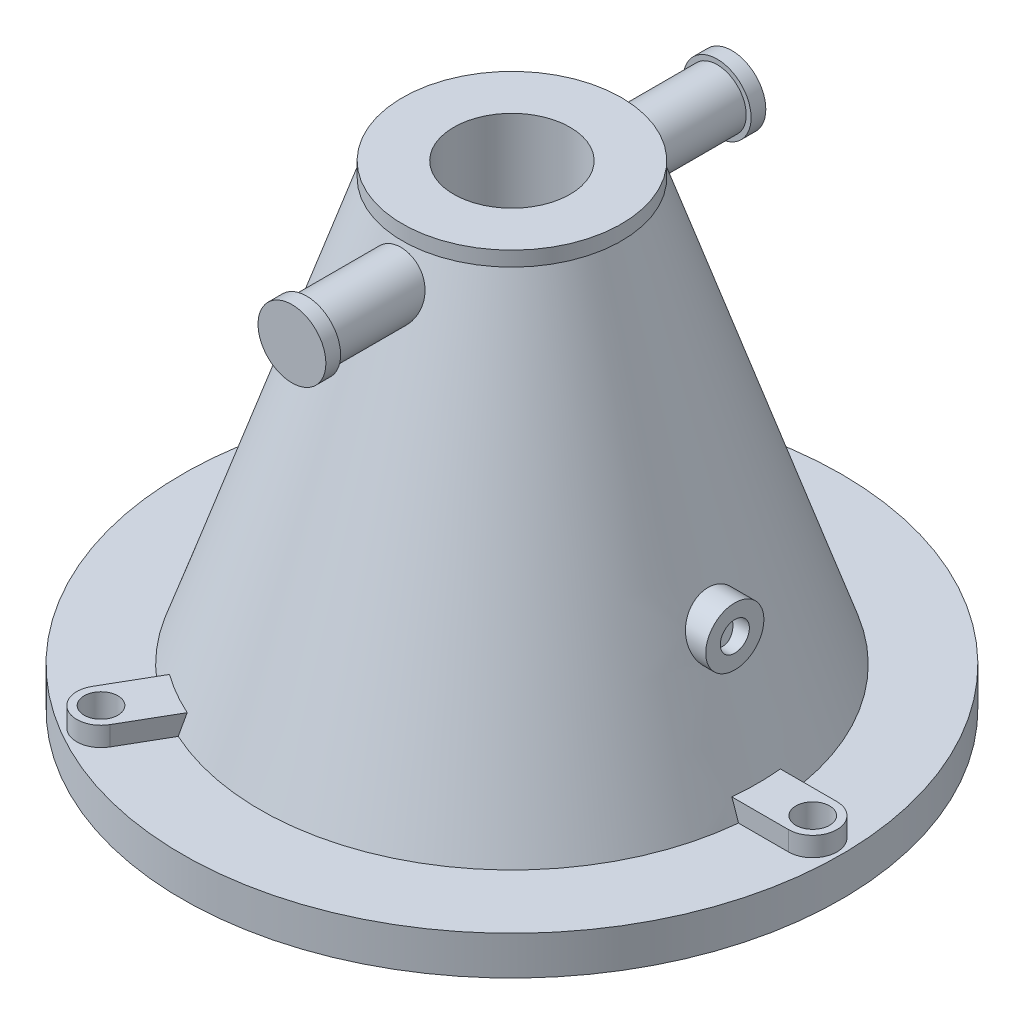
SolidWorks part; units mm, degrees
ref_plane "Front Plane" through (0, 0, 0) normal (0, 0, 1) x (1, 0, 0)
ref_plane "Top Plane" through (0, 0, 0) normal (0, 1, 0) x (1, 0, 0)
ref_plane "Right Plane" through (0, 0, 0) normal (1, 0, 0) x (0, 0, -1)
sketch "Sketch1" plane through (0, 0, 0) normal (0, 0, 1) x (1, 0, 0)
  line L0 (0, 0) -> (0, 2588.207) construction
  line L1 (1.5, 0) -> (2.25, 0)
  line L2 (2.25, 0) -> (2.375, 4.957)
  line L3 (3.3485, 5.1045) -> (6.1731, -3.25)
  line L4 (6.1731, -3.25) -> (8.5, -3.25)
  line L5 (8.5, -3.25) -> (8.5, -2.25)
  line L6 (8.5, -2.25) -> (6.5, -2.25)
  line L7 (2.825, 9) -> (2.825, 8.62)
  line L8 (2.825, 9) -> (1.5, 9)
  line L9 (1.5, 9) -> (1.5, 0)
  line L10 (2.825, 8.62) -> (6.5, -2.25)
  arc A0 (2.375, 4.957) -> (3.3485, 5.1045) centre (2.8748, 4.9444) cw
  dimension "D1" = 1.5
  dimension "D8" = 2.375
  dimension "D2" = 2.25
  dimension "D9" = 0.5
  dimension "D3" = 6.5
  dimension "D4" = 8.5
  dimension "D5" = 1
  dimension "D6" = 12.25
  dimension "D7" = 0.38
  dimension "D10" = 3.25
  dimension "D11" = 2.825
  dimension "D12" = 0.63
revolve "Revolve1" add sketch "Sketch1" angle 360 about L0
sketch "Sketch5" plane through (0, 0, 0) normal (1, 0, 0) x (0, 0, -1)
  line L0 (-8.5, -3.25) -> (8.5, -3.25) construction
  circle A0 centre (0, 1.25) radius 0.75
  circle A1 centre (0, 1.25) radius 0.375
  point P5 (0, 0)
  dimension "D1" = 0.75
  dimension "D2" = 1.5
  dimension "D3" = 4.5
extrude "Boss-Extrude1" add sketch "Sketch5" against normal blind 1.62 from offset 5.75
sketch "Sketch8" plane through (0, -2.25, 0) normal (0, 1, 0) x (1, 0, 0)
  line L0 (7.76, 0.625) -> (6.1835, 0.625)
  line L1 (7.76, -0.625) -> (6.1835, -0.625)
  line L2 (6.1835, 0.625) -> (6.1835, -0.625)
  arc A0 (7.76, -0.625) -> (7.76, 0.625) centre (7.76, 0) ccw
  dimension "D1" = 7.76
  dimension "D2" = 1.25
extrude "Boss-Extrude2" add sketch "Sketch8" along normal blind 0.5
sketch "Sketch10" plane through (0, -1.75, 0) normal (0, 1, 0) x (1, 0, 0)
  circle A0 centre (7.76, 0) radius 0.435
  arc A1 (7.76, -0.625) -> (7.76, 0.625) centre (7.76, 0) ccw construction
  dimension "D1" = 0.87
extrude "Cut-Extrude1" cut sketch "Sketch10" against normal through all
pattern_circular "CirPattern2" count 3 over 360 about axis through (0, -2.25, 0) along (0, -1, 0) of "Boss-Extrude2", "Cut-Extrude1"
sketch "Sketch11" plane through (0, 0, 0) normal (0, 0, 1) x (1, 0, 0)
  line L0 (1.5, 9) -> (-1.5, 9) construction
  circle A0 centre (0, 7.75) radius 0.75
  circle A1 centre (0, 7.75) radius 0.875
  point P3 (0, 0)
  point P7 (0, 0)
  dimension "D1" = 1.75
  dimension "D2" = 1.5
  dimension "D3" = 1.25
extrude "Boss-Extrude4" add sketch "Sketch11" against normal blind 0.38 from offset 5.675 contours A1
extrude "Boss-Extrude6" add sketch "Sketch11<5>" against normal up to next from offset 5.295 separate body contours A0
sketch "Sketch11<5>" plane through (0, 0, 0) normal (0, 0, 1) x (1, 0, 0) same geometry as "Sketch11"
mirror "Mirror5" about plane through (0, 0, 0) normal (0, 0, 1) of bodies 111 109
